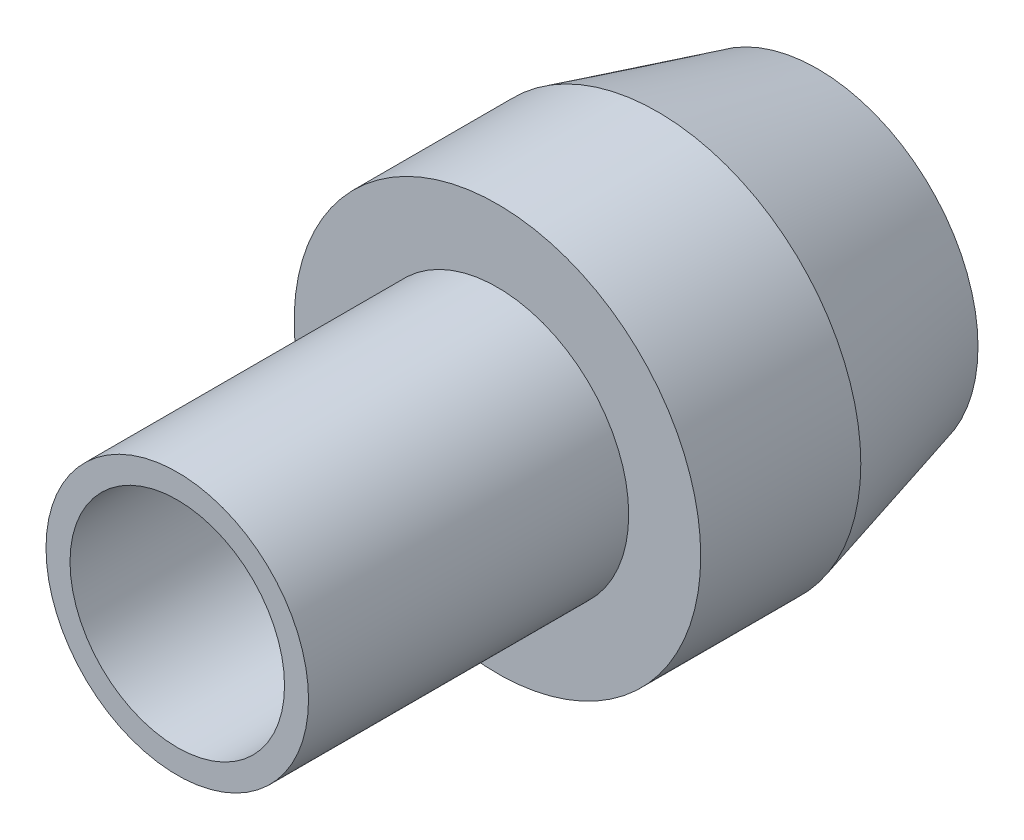
SolidWorks part; units mm, degrees
ref_plane "Front Plane" through (0, 0, 0) normal (0, 0, 1) x (1, 0, 0)
ref_plane "Top Plane" through (0, 0, 0) normal (0, 1, 0) x (1, 0, 0)
ref_plane "Right Plane" through (0, 0, 0) normal (1, 0, 0) x (0, 0, -1)
sketch "Sketch1" plane through (0, 0, 0) normal (0, 0, 1) x (1, 0, 0)
  circle A0 centre (0, 0) radius 6.7
  circle A1 centre (0, 0) radius 8.2
  circle A2 centre (0, 0) radius 12.7
  dimension "D1" = 13.4
  dimension "D2" = 16.4
  dimension "D3" = 25.4
extrude "Boss-Extrude1" add sketch "Sketch1" along normal blind 20 contours A2 A1 | A1 A0 region at (-7.9681, 0, 0) region at (-12.3408, 0, 0)
extrude "Boss-Extrude2" add sketch "Sketch1<4>" along normal blind 20 from surface contours A1 A0 region at (-7.9681, 0, 0) starting at face at (12.7, 0, 20)
sketch "Sketch1<4>" plane through (0, 0, 0) normal (0, 0, 1) x (1, 0, 0) same geometry as "Sketch1"
chamfer "Chamfer1" distance 10 angle 15 1 edges at (12.7, 0, 0) first distance on face at (12.7, 0, 20)
equation "\"D2@Sketch1\"=\"D1@Sketch1\"+3"
equation "\"D3@Sketch1\"=\"D1@Sketch1\"+12"
